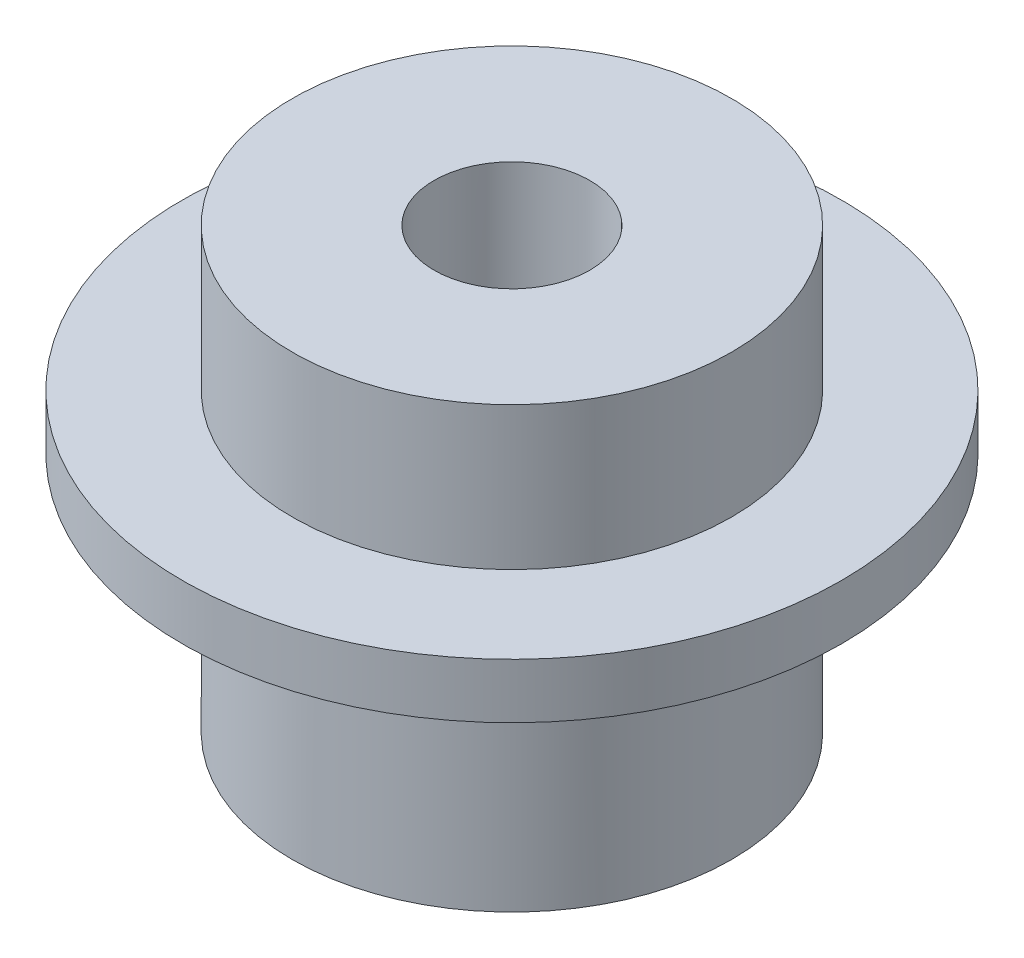
SolidWorks part; units mm, degrees
material "PET"
ref_plane "Front Plane" through (0, 0, 0) normal (1, 0, 0) x (0, 1, 0)
ref_plane "Top Plane" through (0, 0, 0) normal (0, 0, 1) x (0, 1, 0)
ref_plane "Right Plane" through (0, 0, 0) normal (0, 1, 0) x (-1, 0, 0)
sketch "Sketch2" plane through (0, 0, 0) normal (0, 0, 1) x (0, 1, 0)
  line L0 (0, 6.35) -> (0, -6.35) construction
  line L1 (12.7, -6.35) -> (-12.7, -6.35)
  line L2 (12.7, -6.35) -> (12.7, 6.35)
  line L3 (12.7, 6.35) -> (-12.7, 6.35)
  line L4 (-12.7, -6.35) -> (-12.7, 6.35)
  line L5 (12.7, -6.35) -> (-12.7, 6.35) construction
  line L6 (12.7, 6.35) -> (-12.7, -6.35) construction
  line L11 (-8.5725, 9.525) -> (-6.985, 9.525)
  line L12 (-8.5725, 9.525) -> (-8.5725, -9.525)
  line L13 (12.7, -2.25) -> (-12.7, -2.25)
  line L14 (12.7, -2.25) -> (12.7, 2.25)
  line L15 (12.7, 2.25) -> (-12.7, 2.25)
  line L16 (-12.7, -2.25) -> (-12.7, 2.25)
  line L17 (12.7, -2.25) -> (-12.7, 2.25) construction
  line L18 (12.7, 2.25) -> (-12.7, -2.25) construction
  line L19 (-8.5725, -9.525) -> (-6.985, -9.525)
  line L20 (-6.985, 9.525) -> (-6.985, -9.525)
  line L21 (8.5725, -9.525) -> (6.985, -9.525)
  line L22 (6.985, 9.525) -> (6.985, -9.525)
  line L23 (8.5725, 9.525) -> (6.985, 9.525)
  line L24 (8.5725, 9.525) -> (8.5725, -9.525)
  line L25 (-12.7, 0) -> (12.7, 0) construction
  point P0 (0, 0)
  point P6 (0, 0)
  point P11 (0, 0)
  point P16 (-8.5725, 0)
  dimension "D1" = 12.7
  dimension "D2" = 25.4
  dimension "D3" = 25.4
  dimension "D4" = 4.5
  dimension "D5" = 1.5875
  dimension "D6" = 19.05
  dimension "D7" = 6.985
revolve "Revolve2" add sketch "Sketch2" angle 360 about L25 region at (-4.3, 10.6363, 0) region at (-4.3, 7.7788, 0) region at (-4.3, 0, 0) region at (-7.9375, 7.7788, 0) region at (-4.3, -7.7788, 0) region at (-4.3, -10.6362, 0) region at (-7.9375, -7.7788, 0)
sketch "Sketch3" plane through (0, 0, 0) normal (0, 1, 0) x (-1, 0, 0)
  circle A0 centre (0, 0) radius 9.525
extrude "Cut-Extrude1" cut sketch "Sketch3" against normal blind 21.336
